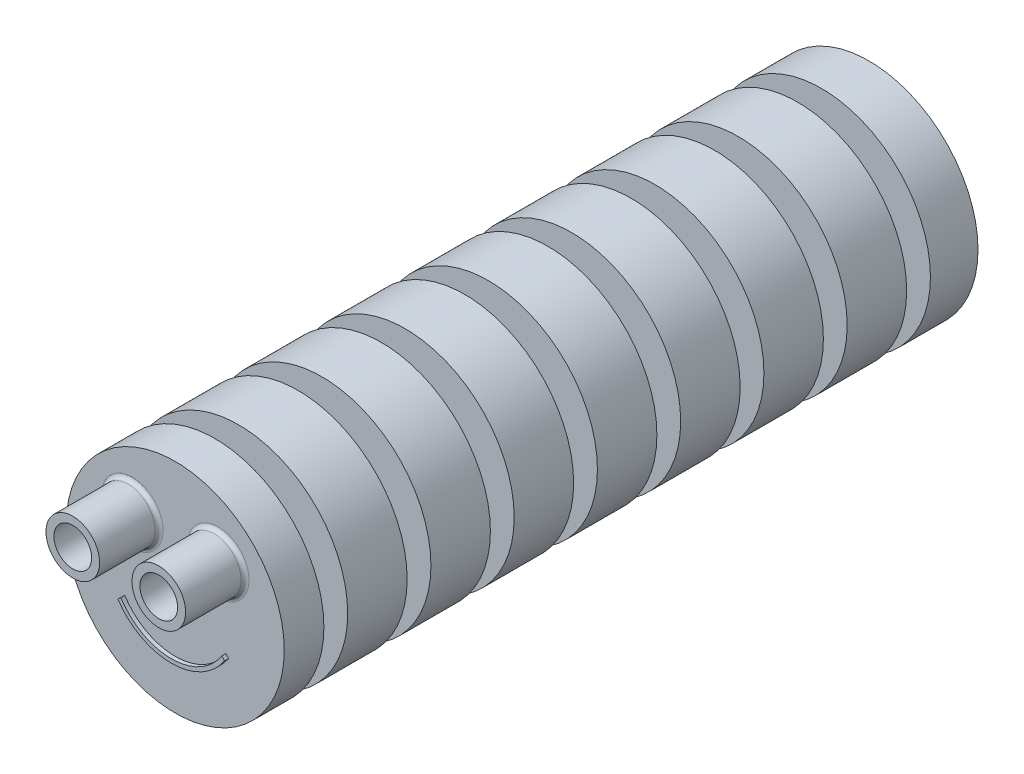
SolidWorks part; units mm, degrees
material "RUBBER 65A"
ref_plane "Front Plane" through (0, 0, 0) normal (0, 0, 1) x (1, 0, 0)
ref_plane "Top Plane" through (0, 0, 0) normal (0, 1, 0) x (1, 0, 0)
ref_plane "Right Plane" through (0, 0, 0) normal (1, 0, 0) x (0, 0, -1)
sketch "Sketch3" plane through (0, 0, 0) normal (0, 0, 1) x (1, 0, 0)
  circle A0 centre (0, 0) radius 27.5
  dimension "D1" = 55
extrude "Boss-Extrude2" add sketch "Sketch3" along normal blind 175
ref_axis "Axis2" through (0, 0, 174.1287) along (0, 0, -1)
sketch "Sketch5" plane through (0, 0, 175) normal (0, 0, 1) x (1, 0, 0)
  circle A0 centre (0, 0) radius 3.175
  dimension "D1" = 6.35
extrude "Cut-Extrude1" cut sketch "Sketch5" against normal through all contours A0
sketch "Sketch4" plane through (0, 0, 0) normal (0, 1, 0) x (1, 0, 0)
  line L0 (0, -175) -> (0, 0) construction
  line L1 (-27.5, -175) -> (27.5, -175) construction
  line L3 (-27.5, -165) -> (-11.5, -165)
  line L4 (-27.5, -165) -> (-27.5, -159)
  line L5 (-27.5, -159) -> (-11.5, -159)
  line L6 (-11.5, -165) -> (-11.5, -159)
  line L63 (-27.5, -144) -> (-27.5, -138)
  line L64 (-27.5, -144) -> (-11.5, -144)
  line L65 (-11.5, -144) -> (-11.5, -138)
  line L66 (-27.5, -138) -> (-11.5, -138)
  line L67 (-27.5, -123) -> (-27.5, -117)
  line L68 (-27.5, -123) -> (-11.5, -123)
  line L69 (-11.5, -123) -> (-11.5, -117)
  line L70 (-27.5, -117) -> (-11.5, -117)
  line L71 (-27.5, -102) -> (-27.5, -96)
  line L72 (-27.5, -102) -> (-11.5, -102)
  line L73 (-11.5, -102) -> (-11.5, -96)
  line L74 (-27.5, -96) -> (-11.5, -96)
  line L75 (-27.5, -81) -> (-27.5, -75)
  line L76 (-27.5, -81) -> (-11.5, -81)
  line L77 (-11.5, -81) -> (-11.5, -75)
  line L78 (-27.5, -75) -> (-11.5, -75)
  line L79 (-27.5, -60) -> (-27.5, -54)
  line L80 (-27.5, -60) -> (-11.5, -60)
  line L81 (-11.5, -60) -> (-11.5, -54)
  line L82 (-27.5, -54) -> (-11.5, -54)
  line L83 (-27.5, -39) -> (-27.5, -33)
  line L84 (-27.5, -39) -> (-11.5, -39)
  line L85 (-11.5, -39) -> (-11.5, -33)
  line L86 (-27.5, -33) -> (-11.5, -33)
  line L87 (-27.5, -18) -> (-27.5, -12)
  line L88 (-27.5, -18) -> (-11.5, -18)
  line L89 (-11.5, -18) -> (-11.5, -12)
  line L90 (-27.5, -12) -> (-11.5, -12)
  line L91 (-27.5, -165) -> (-27.5, -144) construction
  dimension "D1" = 10
  dimension "D2" = 6
  dimension "D3" = 27.5
  dimension "D4" = 16
  dimension "D6" = 21
  dimension "D5" = 8
revolve "Cut-Revolve1" cut sketch "Sketch4" angle 360 about L0
shell "Shell1" thickness 3
sketch "Sketch10" plane through (0, 0, 0) normal (0, 0, -1) x (-1, 0, 0)
  line L0 (0, 27.5) -> (0, -27.5) construction
  line L1 (-27.5, 0) -> (27.5, 0) construction
  line L2 (-1, 27.4818) -> (-1, 3.0134)
  line L3 (1, 3.0134) -> (1, 27.4818)
  line L4 (3.0134, 1) -> (27.4818, 1)
  line L5 (3.0134, -1) -> (27.4818, -1)
  line L6 (-1, -3.0134) -> (-1, -27.4818)
  line L7 (1, -3.0134) -> (1, -27.4818)
  line L8 (-27.4818, -1) -> (-3.0134, -1)
  line L9 (-27.4818, 1) -> (-3.0134, 1)
  circle A0 centre (0, 0) radius 27.5 construction
  circle A1 centre (0, 0) radius 3.175 construction
  arc A2 (-1, -27.4818) -> (1, -27.4818) centre (0, 0) ccw
  arc A3 (27.4818, -1) -> (27.4818, 1) centre (0, 0) ccw
  arc A4 (1, 27.4818) -> (-1, 27.4818) centre (0, 0) ccw
  arc A5 (-27.4818, 1) -> (-27.4818, -1) centre (0, 0) ccw
  arc A6 (-1, -3.0134) -> (1, -3.0134) centre (0, 0) ccw
  arc A7 (-3.0134, 1) -> (-3.0134, -1) centre (0, 0) ccw
  arc A8 (1, 3.0134) -> (-1, 3.0134) centre (0, 0) ccw
  arc A9 (3.0134, -1) -> (3.0134, 1) centre (0, 0) ccw
  dimension "D1" = 1
  dimension "D2" = 1
  dimension "D3" = 1
  dimension "D4" = 1
  dimension "D5" = 1
extrude "Boss-Extrude3" add sketch "Sketch10" against normal up to surface (175 mm away) up to face at (3.175, 0, 175)
sketch "Sketch11" plane through (0, 0, 0) normal (1, 0, 0) x (0, 0, -1)
  line L0 (-117, 27.4818) -> (-117, 1) construction
  line L1 (-165, 30.0791) -> (-159, 30.0791)
  line L2 (-165, 30.0791) -> (-165, 11.4564)
  line L3 (-165, 11.4564) -> (-159, 11.4564)
  line L4 (-159, 30.0791) -> (-159, 11.4564)
  line L5 (-144, 30.0191) -> (-138, 30.0191)
  line L6 (-144, 30.0191) -> (-144, 11.4564)
  line L7 (-144, 11.4564) -> (-138, 11.4564)
  line L8 (-138, 30.0191) -> (-138, 11.4564)
  line L9 (-123, 30.1992) -> (-117, 30.1992)
  line L10 (-123, 30.1992) -> (-123, 11.4755)
  line L11 (-123, 11.4755) -> (-117, 11.4755)
  line L12 (-117, 30.1992) -> (-117, 11.4755)
  line L13 (-117, 11.4564) -> (-117, 1) construction
  line L14 (-75, 11.4564) -> (-75, 1) construction
  line L15 (-102, 30.5593) -> (-96, 30.5593)
  line L16 (-102, 30.5593) -> (-102, 11.4564)
  line L17 (-102, 11.4564) -> (-96, 11.4564)
  line L18 (-96, 30.5593) -> (-96, 11.4564)
  line L19 (-81, 30.9195) -> (-75, 30.9195)
  line L20 (-81, 30.9195) -> (-81, 11.4755)
  line L21 (-81, 11.4755) -> (-75, 11.4755)
  line L22 (-75, 30.9195) -> (-75, 11.4755)
  line L23 (-75, 27.4818) -> (-75, 1) construction
  line L25 (-60, 31.9241) -> (-54, 31.9241)
  line L26 (-60, 31.9241) -> (-60, 11.4564)
  line L27 (-60, 11.4564) -> (-54, 11.4564)
  line L28 (-54, 31.9241) -> (-54, 11.4564)
  line L29 (-39, 30.6232) -> (-33, 30.6232)
  line L30 (-39, 30.6232) -> (-39, 11.4564)
  line L31 (-39, 11.4564) -> (-33, 11.4564)
  line L32 (-33, 30.6232) -> (-33, 11.4564)
  line L33 (-18, 31.5847) -> (-12, 31.5847)
  line L34 (-18, 31.5847) -> (-18, 11.4564)
  line L35 (-18, 11.4564) -> (-12, 11.4564)
  line L36 (-12, 31.5847) -> (-12, 11.4564)
revolve "Cut-Revolve2" cut sketch "Sketch11" angle 360 about axis through (0, 0, 174.1287) along (0, 0, -1)
sketch "Sketch12" plane through (0, 0, 0) normal (0, 1, 0) x (1, 0, 0)
  line L0 (24.4796, -172) -> (6.0935, -172) construction
  line L1 (24.7296, -168) -> (23.4796, -168)
  line L2 (24.7296, -168) -> (24.7296, -172)
  line L3 (24.7296, -172) -> (23.4796, -172)
  line L4 (23.4796, -168) -> (23.4796, -172)
  line L5 (0, 0) -> (0, -175) construction
  line L6 (-3.175, -175) -> (3.175, -175) construction
  line L7 (24.4796, -156) -> (8.441, -156) construction
  line L8 (24.4796, -9) -> (8.441, -9) construction
  line L9 (24.7296, -3) -> (23.4796, -3)
  line L10 (24.7296, -3) -> (24.7296, -9)
  line L11 (24.7296, -9) -> (23.4796, -9)
  line L12 (23.4796, -3) -> (23.4796, -9)
  line L13 (24.7296, -147) -> (23.4796, -147)
  line L14 (24.7296, -147) -> (24.7296, -156)
  line L15 (24.7296, -156) -> (23.4796, -156)
  line L16 (23.4796, -147) -> (23.4796, -156)
  line L17 (24.4796, -135) -> (8.441, -135) construction
  line L18 (24.7296, -126) -> (23.4796, -126)
  line L19 (24.7296, -126) -> (24.7296, -135)
  line L20 (24.7296, -135) -> (23.4796, -135)
  line L21 (23.4796, -126) -> (23.4796, -135)
  line L22 (24.4796, -114) -> (8.441, -114) construction
  line L23 (24.7296, -105) -> (23.4796, -105)
  line L24 (24.7296, -105) -> (24.7296, -114)
  line L25 (24.7296, -114) -> (23.4796, -114)
  line L26 (23.4796, -105) -> (23.4796, -114)
  line L27 (24.4796, -93) -> (8.441, -93) construction
  line L28 (24.7296, -84) -> (23.4796, -84)
  line L29 (24.7296, -84) -> (24.7296, -93)
  line L30 (24.7296, -93) -> (23.4796, -93)
  line L31 (23.4796, -84) -> (23.4796, -93)
  line L32 (24.4796, -72) -> (8.441, -72) construction
  line L33 (24.7296, -63) -> (23.4796, -63)
  line L34 (24.7296, -63) -> (24.7296, -72)
  line L35 (24.7296, -72) -> (23.4796, -72)
  line L36 (23.4796, -63) -> (23.4796, -72)
  line L37 (24.4796, -51) -> (8.441, -51) construction
  line L38 (24.7296, -42) -> (23.4796, -42)
  line L39 (24.7296, -42) -> (24.7296, -51)
  line L40 (24.7296, -51) -> (23.4796, -51)
  line L41 (23.4796, -42) -> (23.4796, -51)
  line L42 (24.4796, -30) -> (8.441, -30) construction
  line L43 (24.7296, -21) -> (23.4796, -21)
  line L44 (24.7296, -21) -> (24.7296, -30)
  line L45 (24.7296, -30) -> (23.4796, -30)
  line L46 (23.4796, -21) -> (23.4796, -30)
  dimension "D1" = 1.25
  dimension "D2" = 1.25
  dimension "D3" = 1.25
  dimension "D4" = 1.25
  dimension "D5" = 1.25
  dimension "D6" = 1.25
  dimension "D7" = 1.25
  dimension "D8" = 1.25
  dimension "D9" = 1.25
revolve "Revolve1" add sketch "Sketch12" angle 360 about L5
ref_plane "Plane1" through (0, 0, 0) normal (-0.7071, -0.7071, 0) x (0, 0, -1)
ref_plane "Plane2" through (0, 0, 0) normal (-0.7071, 0.7071, 0) x (0, 0, -1)
sketch "Sketch13" plane through (0, 0, 175) normal (0, 0, 1) x (1, 0, 0)
  line L0 (0, 27.5) -> (0, -27.5) construction
  line L1 (27.5, 0) -> (-27.5, 0) construction
  line L2 (0, 0) -> (19.4454, 19.4454) construction
  line L3 (22.3322, 22.3322) -> (-22.3322, -22.3322) construction
  circle A0 centre (10.8453, 10.8453) radius 6.7625
  circle A1 centre (10.8453, 10.8453) radius 4.7625
  circle A2 centre (0, 0) radius 15.3375 construction
  circle A3 centre (0, 0) radius 27.5 construction
  dimension "D1" = 2
  dimension "D2" = 9.525
  dimension "D3" = 30.675
extrude "Boss-Extrude4" add sketch "Sketch13" along normal blind 15
sketch "Sketch14" plane through (0, 0, 190) normal (0, 0, 1) x (1, 0, 0)
  circle A0 centre (10.8453, 10.8453) radius 4.7625
  dimension "D1" = 9.525
extrude "Cut-Extrude2" cut sketch "Sketch14" against normal blind 18
pattern_circular "CirPattern1" count 2 over 90 about axis through (0, 0, 174.1287) along (0, 0, -1) of "Boss-Extrude4", "Cut-Extrude2" reverse direction yes
fillet "Fillet1" radius 1 2 edges at (17.6078, 10.8453, 175) (-10.8453, 17.6078, 175)
sketch "Sketch15" plane through (0, 0, 175) normal (0, 0, 1) x (1, 0, 0)
  line L0 (-12.732, -8.1342) -> (12.732, -8.1342) construction
  line L1 (-12.732, -8.1342) -> (-13.4531, -8.8271)
  line L2 (12.732, -8.1342) -> (13.4306, -8.8612)
  arc A0 (-12.732, -8.1342) -> (12.732, -8.1342) centre (0, 0) ccw
  circle A2 centre (0, 0) radius 27.5 construction
  arc A3 (-13.4531, -8.8271) -> (13.4306, -8.8612) centre (0, 0) ccw
  point P8 (14.0433, -10.3918)
  point P9 (0, 0)
  dimension "D1" = 90
  dimension "D2" = 1
extrude "Boss-Extrude5" add sketch "Sketch15" along normal blind 1
equation "\"inwall\"= .75"
equation "\"outwall\"=2"
